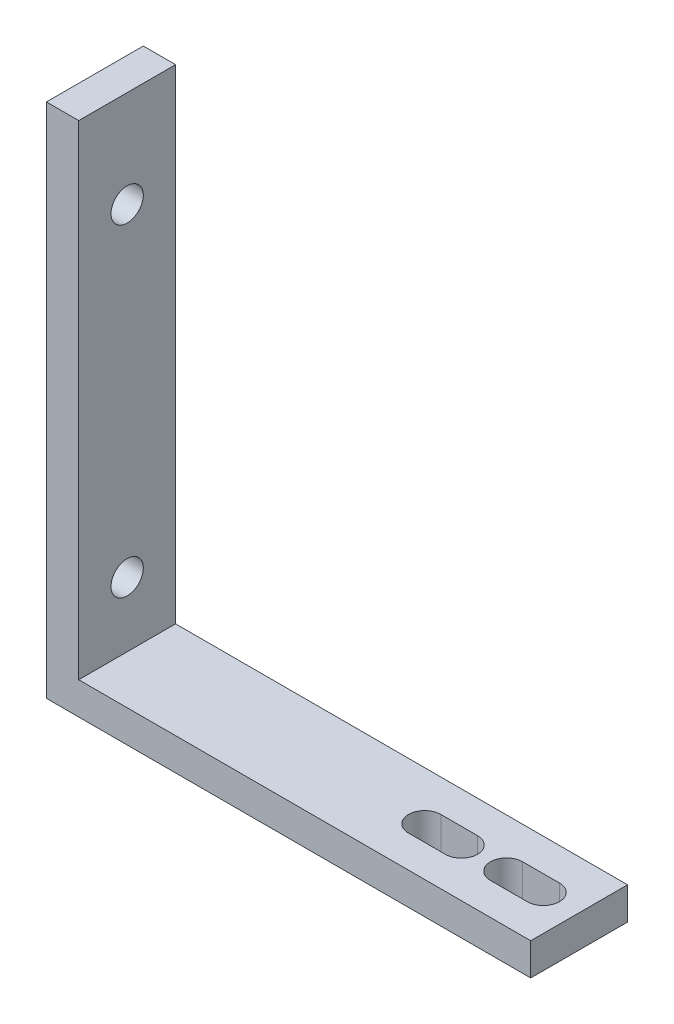
SolidWorks part; units mm, degrees
ref_plane "Front Plane" through (0, 0, 0) normal (0, 0, 1) x (1, 0, 0)
ref_plane "Top Plane" through (0, 0, 0) normal (0, 1, 0) x (1, 0, 0)
ref_plane "Right Plane" through (0, 0, 0) normal (1, 0, 0) x (0, 0, -1)
sketch "Sketch1" plane through (0, 0, 0) normal (0, 1, 0) x (1, 0, 0)
  line L1 (0, 0) -> (75, 0)
  line L2 (0, 0) -> (0, 15)
  line L3 (0, 15) -> (75, 15)
  line L4 (75, 0) -> (75, 15)
  dimension "D1" = 15
  dimension "D2" = 75
extrude "Boss-Extrude1" add sketch "Sketch1" along normal blind 5
sketch "Sketch2" plane through (0, 5, 0) normal (0, 1, 0) x (1, 0, 0)
  line L0 (0, 15) -> (5, 15)
  line L1 (75, 15) -> (0, 15) construction
  line L2 (0, 0) -> (5, 0)
  line L3 (0, 0) -> (75, 0) construction
  line L4 (5, 15) -> (5, 0)
  line L5 (0, 15) -> (0, 0)
extrude "Boss-Extrude2" add sketch "Sketch2" along normal blind 75
sketch "Sketch3" plane through (0, 0, 0) normal (0, -1, 0) x (-1, 0, 0)
  line L0 (0, 7.5) -> (-75, 7.5)
  line L1 (0, 15) -> (0, 0) construction
  line L2 (-75, 0) -> (-75, 15) construction
sketch "Sketch4" plane through (0, 0, 0) normal (-1, 0, 0) x (0, 0, 1)
  line L0 (-7.5, 80) -> (-7.5, 0)
  line L1 (-15, 80) -> (0, 80) construction
  line L2 (-15, 0) -> (0, 0) construction
  line L3 (-7.5, 0) -> (-7.5, 15)
  line L4 (-7.5, 80) -> (-7.5, 65)
hole_wizard "Ø5.0mm Dowel Hole1" positions "Sketch5" profile "Sketch6" hole size "Ø5.0" standard "ANSI Metric" end condition up to next
sketch "Sketch5" plane through (0, 0, 0) normal (-1, 0, 0) x (0, 0, 1)
  point P0 (-7.5, 65)
  point P3 (-7.5, 15)
sketch "Sketch6" plane through (0, 65, -7.5) normal (0, 1, 0) x (0, 0, 1)
  line L0 (0, 0) -> (0, 5)
  line L1 (0, 5) -> (2.5, 5)
  line L2 (2.5, 5) -> (2.5, 0)
  line L5 (2.5, 0) -> (0, 0)
  line L11 (0, -6.35) -> (0, 107.95) construction
  dimension "Thru Hole Dia." = 5
  dimension "Thru Hole Depth" = 5
hole_wizard "Ø6.0mm Dowel Slot1" positions "Sketch9" profile "Sketch8" size "Ø5.0" standard "ANSI Metric" slot yes end condition up to next
sketch "Sketch9" plane through (0, 0, 0) normal (0, -1, 0) x (-1, 0, 0)
  line L1 (-48.5943, 7.4749) -> (-59.2943, 7.4749) construction
  point P5 (-53.9443, 7.4749)
  point P10 (-66.6443, 7.465)
  point P14 (0, 0)
  point P15 (0, 0)
  point P16 (0, 0)
  point P17 (0, 0)
  point P20 (0, 0)
  dimension "D2" = 10.7
sketch "Sketch8" plane through (53.9443, 0, -7.4749) normal (1, 0, 0) x (0, 0, -1)
  line L0 (0, 0) -> (0, 5)
  line L1 (0, 5) -> (2.5, 5)
  line L2 (2.5, 5) -> (2.5, 0)
  line L5 (2.5, 0) -> (0, 0)
  line L11 (0, -6.35) -> (0, 107.95) construction
  dimension "Thru Hole Dia." = 5
  dimension "Thru Hole Depth" = 5
